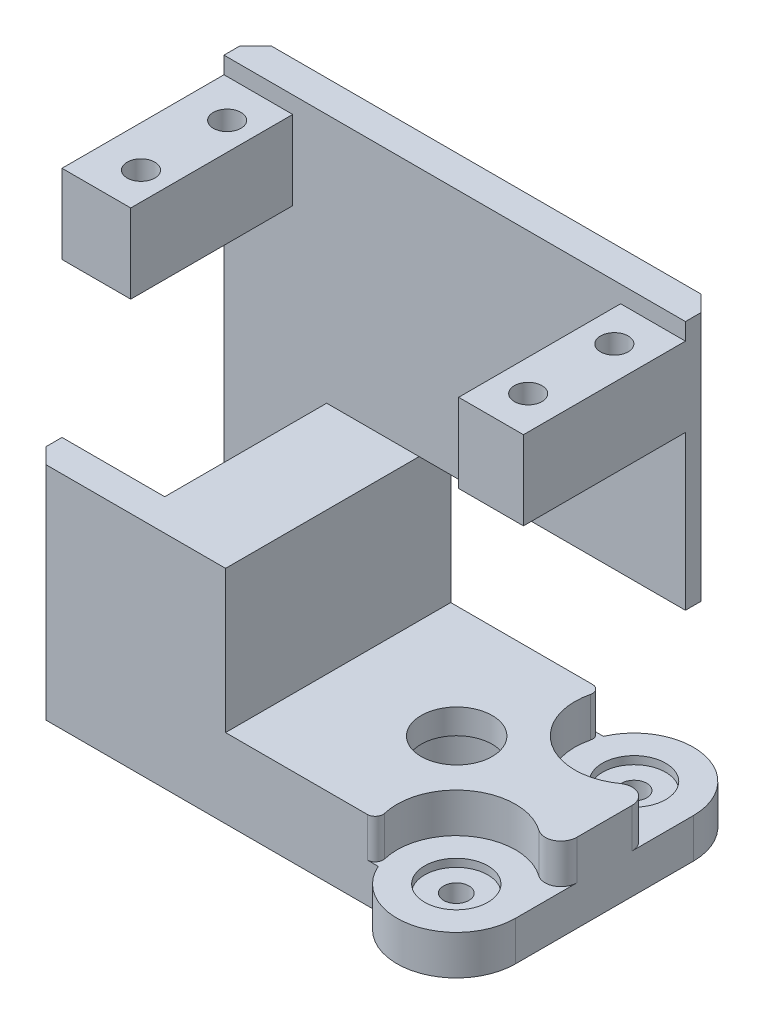
SolidWorks part; units mm, degrees
material "ABS"
ref_plane "Płaszczyzna przednia" through (0, 0, 0) normal (0, 0, 1) x (1, 0, 0)
ref_plane "Płaszczyzna górna" through (0, 0, 0) normal (0, 1, 0) x (1, 0, 0)
ref_plane "Płaszczyzna prawa" through (0, 0, 0) normal (1, 0, 0) x (0, 0, -1)
sketch "Szkic1" plane through (0, 0, 0) normal (0, 1, 0) x (1, 0, 0)
  line L0 (-55, 0) -> (55, 0) construction
  line L1 (-39.7, 14.25) -> (11.95, 14.25)
  line L2 (-39.7, 14.25) -> (-39.7, -14.25)
  line L3 (-39.7, -14.25) -> (11.95, -14.25)
  line L4 (18.7, 7.5) -> (18.7, -7.5)
  line L5 (0, 0) -> (15.3306, 0) construction
  line L6 (18.7, 7.5) -> (11.95, 14.25)
  line L7 (18.7, -7.5) -> (11.95, -14.25)
  circle A0 centre (0, 0) radius 4.5
  dimension "D1" = 9
  dimension "D2" = 58.4
  dimension "D3" = 28.5
  dimension "D4" = 18.7
  dimension "D5" = 15
  dimension "D6" = 45
extrude "Dodanie-wyciągnięcie1" add sketch "Szkic1" along normal blind 10
sketch "Szkic3" plane through (0, 0, 0) normal (0, -1, 0) x (1, 0, 0)
  circle A0 centre (0, 0) radius 6.5
  dimension "D1" = 13
extrude "Wytnij-wyciągnięcie9" cut sketch "Szkic3" against normal offset from surface (6.85 mm away) 3.15 contours A0 up to face at (-3.0167, 10, 0)
sketch "Szkic4" plane through (0, 10, 0) normal (0, 1, 0) x (1, 0, 0)
  line L0 (-39.7, -14.25) -> (11.95, -14.25) construction
  line L1 (-39.7, 14.25) -> (-15, 14.25)
  line L2 (-39.7, 14.25) -> (-39.7, -14.25)
  line L3 (-39.7, -14.25) -> (-15, -14.25)
  line L4 (-15, 14.25) -> (-15, -14.25)
  dimension "D1" = 15
extrude "Dodanie-wyciągnięcie2" add sketch "Szkic4" along normal blind 18
sketch "Szkic6" plane through (0, 28, 0) normal (0, 1, 0) x (1, 0, 0)
  line L0 (18.7, -7.5) -> (18.7, 7.5) construction
  line L1 (-39.7, 14.25) -> (18.7, 14.25)
  line L2 (-39.7, 14.25) -> (-39.7, 10.25)
  line L3 (-39.7, 10.25) -> (18.7, 10.25)
  line L4 (18.7, 14.25) -> (18.7, 10.25)
  dimension "D1" = 10.25
extrude "Dodanie-wyciągnięcie3" add sketch "Szkic6" along normal blind 31.65 contours L4 L3 L2 L1
sketch "Szkic7" plane through (0, 0, -10.25) normal (0, 0, 1) x (1, 0, 0)
  line L0 (18.7, 59.65) -> (18.7, 28) construction
  line L1 (18.7, 57.5) -> (10.5, 57.5)
  line L2 (18.7, 57.5) -> (18.7, 47.5)
  line L3 (18.7, 47.5) -> (10.5, 47.5)
  line L4 (10.5, 57.5) -> (10.5, 47.5)
  line L5 (0, -55) -> (0, 55) construction
  line L6 (-39.7, 59.65) -> (-39.7, 28) construction
  line L7 (-15, 28) -> (18.7, 28) construction
  line L8 (-39.7, 57.5) -> (-31, 57.5)
  line L9 (-39.7, 57.5) -> (-39.7, 47.5)
  line L10 (-39.7, 47.5) -> (-31, 47.5)
  line L11 (-31, 57.5) -> (-31, 47.5)
  dimension "D1" = 29.5
  dimension "D2" = 10
  dimension "D3" = 10.5
  dimension "D4" = 31
extrude "Dodanie-wyciągnięcie4" add sketch "Szkic7" along normal blind 20.5
sketch "Szkic8" plane through (0, 57.5, 0) normal (0, 1, 0) x (1, 0, 0)
  line L0 (-31, -10.25) -> (-31, 10.25) construction
  line L1 (-31, 10.25) -> (-39.7, 10.25) construction
  line L2 (-34.5, 5.45) -> (19.9035, 5.45) construction
  line L3 (10.5, -10.25) -> (10.5, 10.25) construction
  line L4 (-55, 0) -> (55, 0) construction
  circle A0 centre (-34.5, 5.45) radius 1.75
  circle A1 centre (14.5, 5.45) radius 1.75
  circle A2 centre (14.5, -5.45) radius 1.75
  circle A3 centre (-34.5, -5.45) radius 1.75
  dimension "D1" = 3.5
  dimension "D2" = 3.5
  dimension "D4" = 3.5
  dimension "D5" = 4
  dimension "D3" = 4.8
extrude "Wytnij-wyciągnięcie3" cut sketch "Szkic8" against normal up to next
chamfer "Sfazowanie1" distance 2 angle 45 3 edges at (18.7, 43.825, -14.25) (-39.7, 29.825, -14.25) (-39.7, 14, 14.25)
ref_axis "Oś1" through (18.7, 28, -12.25) along (0, 1, 0)
sketch "Szkic9" plane through (0, 0, 0) normal (0, -1, 0) x (1, 0, 0)
  line L3 (18.7, -7.5) -> (11.95, -14.25)
  line L4 (11.95, -14.25) -> (4.3261, -14.25)
  line L7 (-15, -14.25) -> (16.7, -14.25) construction
  line L16 (18.7, -7.5) -> (18.7, -11.25)
  line L18 (18.7, -12.25) -> (18.7, -10.25) construction
  line L19 (55, 0) -> (-55, 0) construction
  line L20 (18.7, 7.5) -> (18.7, 11.25)
  line L21 (11.95, 14.25) -> (4.3261, 14.25)
  line L22 (18.7, 7.5) -> (11.95, 14.25)
  arc A6 (4.3261, -14.25) -> (18.7, -11.25) centre (11.2, -11.25) ccw
  arc A7 (4.3261, 14.25) -> (18.7, 11.25) centre (11.2, 11.25) cw
  dimension "D2" = 7.5
  dimension "D3" = 3
extrude "Dodanie-wyciągnięcie5" add sketch "Szkic9" against normal up to vertex (10 mm away) up to point (11.95, 10, 14.25)
sketch "Szkic12" plane through (0, 0, 0) normal (0, -1, 0) x (1, 0, 0)
  line L0 (55, 0) -> (-55, 0) construction
  circle A0 centre (11.2, -11.25) radius 1.6
  arc A1 (4.3261, -14.25) -> (18.7, -11.25) centre (11.2, -11.25) ccw construction
  circle A2 centre (11.2, 11.25) radius 1.6
  dimension "D1" = 3.2
extrude "Wytnij-wyciągnięcie4" cut sketch "Szkic12" against normal up to next
sketch "Szkic14" plane through (0, 10, 0) normal (0, 1, 0) x (1, 0, 0)
  line L0 (18.7, -11.25) -> (18.7, 11.25) construction
  line L1 (-32.12, 0) -> (32.12, 0) construction
  circle A0 centre (11.2, -11.25) radius 7.5
  circle A1 centre (11.2, 11.25) radius 7.5
extrude "Wytnij-wyciągnięcie6" cut sketch "Szkic14" against normal blind 5
sketch "Szkic13" plane through (0, 5, 0) normal (0, 1, 0) x (1, 0, 0)
  line L0 (-32.12, 0) -> (32.12, 0) construction
  circle A0 centre (11.2, 11.25) radius 4
  circle A1 centre (11.2, -11.25) radius 4
  dimension "D1" = 8
extrude "Wytnij-wyciągnięcie5" cut sketch "Szkic13" against normal blind 1
fillet "Zaokrąglenie1" radius 2 2 edges at (18.7, 7.5, -11.25) (18.7, 7.5, 11.25)
fillet "Zaokrąglenie2" radius 1 2 edges at (4.3261, 7.5, -14.25) (4.3261, 7.5, 14.25)
sketch "Szkic15" plane through (-39.7, 0, 0) normal (-1, 0, 0) x (0, 0, 1)
  line L0 (0, -32.12) -> (0, 32.12) construction
  line L1 (-10.25, 28) -> (10.25, 28)
  line L2 (-10.25, 28) -> (-10.25, 6)
  line L3 (-10.25, 6) -> (10.25, 6)
  line L4 (10.25, 28) -> (10.25, 6)
  line L5 (-10.25, 28) -> (10.25, 6) construction
  line L6 (-10.25, 6) -> (10.25, 28) construction
  line L7 (-10.25, 28) -> (12.25, 28) construction
  line L8 (-10.25, 47.5) -> (-10.25, 28) construction
  line L9 (-12.25, 0) -> (12.25, 0) construction
  point P0 (0, 17)
  dimension "D1" = 6
  dimension "D2" = 22
extrude "Wytnij-wyciągnięcie7" cut sketch "Szkic15" against normal blind 13
sketch "Szkic16" plane through (0, 6, 0) normal (0, 1, 0) x (1, 0, 0)
  line L0 (-32.12, 0) -> (32.12, 0) construction
  line L1 (-39.7, 12.25) -> (-39.7, -12.25) construction
  circle A0 centre (-33.2, 0) radius 1.6
  dimension "D1" = 3.2
  dimension "D2" = 6.5
extrude "Wytnij-wyciągnięcie8" cut sketch "Szkic16" against normal up to next
sketch "Szkic18" plane through (0, 0, 0) normal (0, -1, 0) x (1, 0, 0)
  point P0 (0, 0)
  point P1 (0, 0)
sketch "Szkic19" plane through (0, 0, 0) normal (1, 0, 0) x (0, 0, -1)
  point P0 (0, 48.407)
  point P1 (0, 48.407)
  point P2 (0, 48.407)
